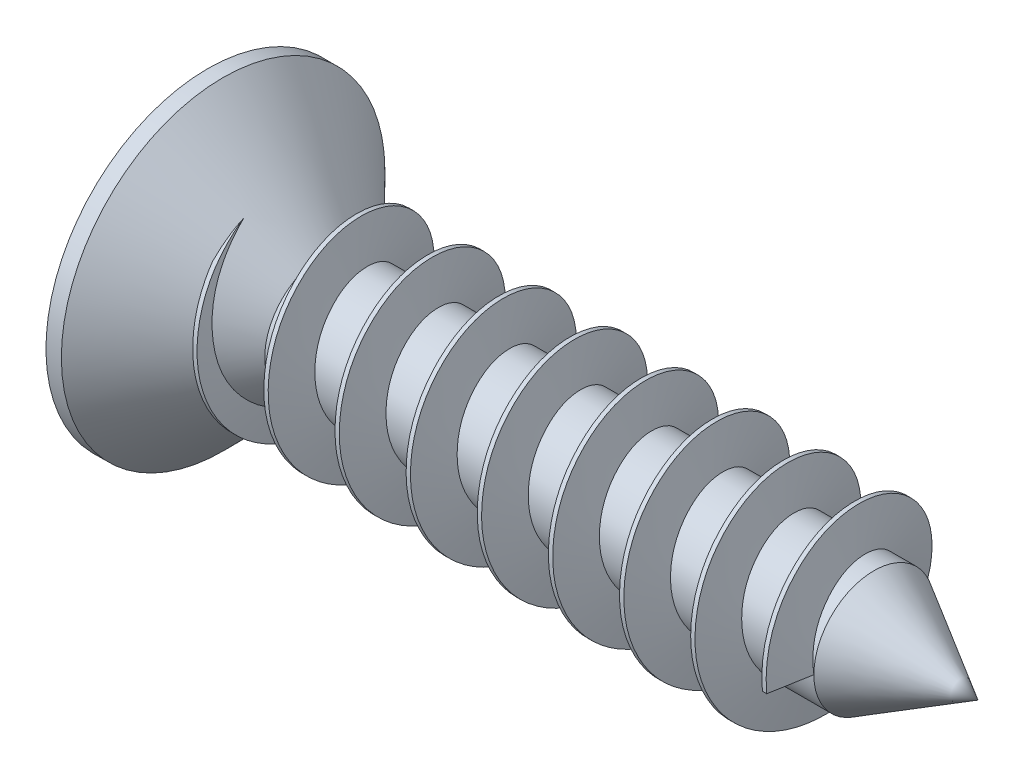
SolidWorks part; units mm, degrees
material "AISI 304"
ref_plane "Front Plane" through (0, 0, 0) normal (0, 0, 1) x (1, 0, 0)
ref_plane "Top Plane" through (0, 0, 0) normal (0, 1, 0) x (1, 0, 0)
ref_plane "Right Plane" through (0, 0, 0) normal (1, 0, 0) x (0, 0, -1)
sketch "Sketch1" plane through (0, 0, 0) normal (0, 0, 1) x (1, 0, 0)
  line L0 (0, 0) -> (0, 2.1)
  line L1 (0, 2.1) -> (0.2, 2.1)
  line L2 (0.2, 2.1) -> (1.52, 0.78)
  line L5 (1.52, 0.78) -> (8.649, 0.78)
  line L6 (8.649, 0.78) -> (10, 0)
  line L7 (10, 0) -> (0, 0) construction
  line L8 (0, 0) -> (10, 0)
  dimension "D1" = 4.2
  dimension "D2" = 1.56
  dimension "D3" = 10
  dimension "D4" = 45
  dimension "D5" = 0.2
  dimension "D6" = 30
revolve "Body" add sketch "Sketch1" angle 360 about L7
thread "Thread" pitch 0.9235 start angle 0, offset 0, length 0, pitch 0.9235, diameter 1.56
ref_plane "Plane1" through (8.649, 0, 0.78) normal (0, -1, 0) x (0, 0, 1)
sketch "Thread Profile1" plane through (8.649, 0, 0.78) normal (0, -1, 0) x (0, 0, 1)
  line L0 (0, 0) -> (0, 0.9235) construction
  line L1 (0, 0) -> (0.52, 0.0917)
  line L2 (0.52, 0.0917) -> (0.52, 0.1479)
  line L3 (0.52, 0.1479) -> (0, 0.2396)
  line L4 (0.52, 0.1198) -> (0, 0.1198) construction
  line L11 (0, 0) -> (0, 0.2396)
  point P2 (0, 0)
  dimension "Pitch" = 0.9235
  dimension "Profile_Angle" = 20
  dimension "Profile_Land" = 0.0562
  dimension "Profile_Height" = 0.52
sketch "Sketch5" plane through (0, 0, 0) normal (-1, 0, 0) x (0, 0, 1)
  line L0 (-1.3, 0) -> (1.3, 0)
  line L1 (0, 1.3) -> (0, -1.3)
  point P5 (0, 0)
  point P7 (0, 0)
  dimension "D1" = 2.6
extrude "CrossScrewDrive" cut sketch "Sketch5" against normal blind 1 draft 10 thin thin type mid plane wall 0.6
